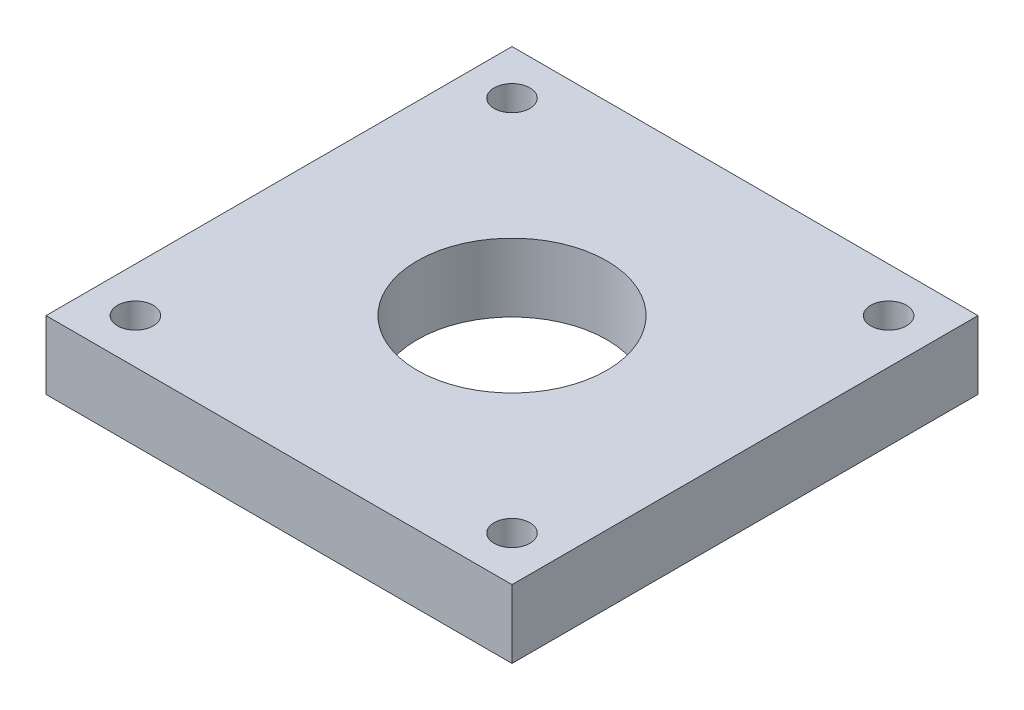
SolidWorks part; units mm, degrees
ref_plane "Front Plane" through (0, 0, 0) normal (0, 0, 1) x (1, 0, 0)
ref_plane "Top Plane" through (0, 0, 0) normal (0, 1, 0) x (1, 0, 0)
ref_plane "Right Plane" through (0, 0, 0) normal (1, 0, 0) x (0, 0, -1)
sketch "Sketch1" plane through (0, 0, 0) normal (0, 1, 0) x (1, 0, 0)
  line L1 (-43, 43) -> (43, 43)
  line L2 (-43, 43) -> (-43, -43)
  line L3 (-43, -43) -> (43, -43)
  line L4 (43, 43) -> (43, -43)
  line L5 (-43, 43) -> (43, -43) construction
  line L6 (-43, -43) -> (43, 43) construction
  circle A0 centre (0, 0) radius 17.5
  point P0 (0, 0)
  dimension "D3" = 35
  dimension "D1" = 86
  dimension "D2" = 86
extrude "Boss-Extrude1" add sketch "Sketch1" along normal blind 12.6
sketch "Sketch2" plane through (0, 12.6, 0) normal (0, 1, 0) x (1, 0, 0)
  circle A0 centre (-34.75, -34.75) radius 3.3 construction
  circle A1 centre (-34.75, 34.75) radius 3.3 construction
  circle A2 centre (34.75, -34.75) radius 3.3 construction
  circle A3 centre (34.75, 34.75) radius 3.3 construction
  circle A4 centre (-34.75, -34.75) radius 3.3
  circle A5 centre (-34.75, 34.75) radius 3.3
  circle A6 centre (34.75, -34.75) radius 3.3
  circle A7 centre (34.75, 34.75) radius 3.3
extrude "Cut-Extrude1" cut sketch "Sketch2" against normal up to next
sketch "Sketch3" plane through (0, 0, 0) normal (0, 1, 0) x (1, 0, 0)
  line L4 (43, -43) -> (43, 43)
  line L5 (43, 43) -> (-43, 43)
  line L6 (-43, 43) -> (-43, -43)
  line L7 (-43, -43) -> (43, -43)
  line L8 (43, -43) -> (43, 43)
  line L9 (43, 43) -> (-43, 43)
  line L10 (-43, 43) -> (-43, -43)
  line L11 (-43, -43) -> (43, -43)
  circle A0 centre (-34.75, -34.75) radius 3.3 construction
  circle A1 centre (34.75, -34.75) radius 3.3 construction
  circle A2 centre (34.75, 34.75) radius 3.3 construction
  circle A3 centre (-34.75, 34.75) radius 3.3 construction
  circle A4 centre (0, 0) radius 17.5 construction
  circle A5 centre (-34.75, -34.75) radius 3.3
  circle A6 centre (34.75, -34.75) radius 3.3
  circle A7 centre (34.75, 34.75) radius 3.3
  circle A8 centre (-34.75, 34.75) radius 3.3
  circle A9 centre (0, 0) radius 17.5
  dimension "D1" = 0
